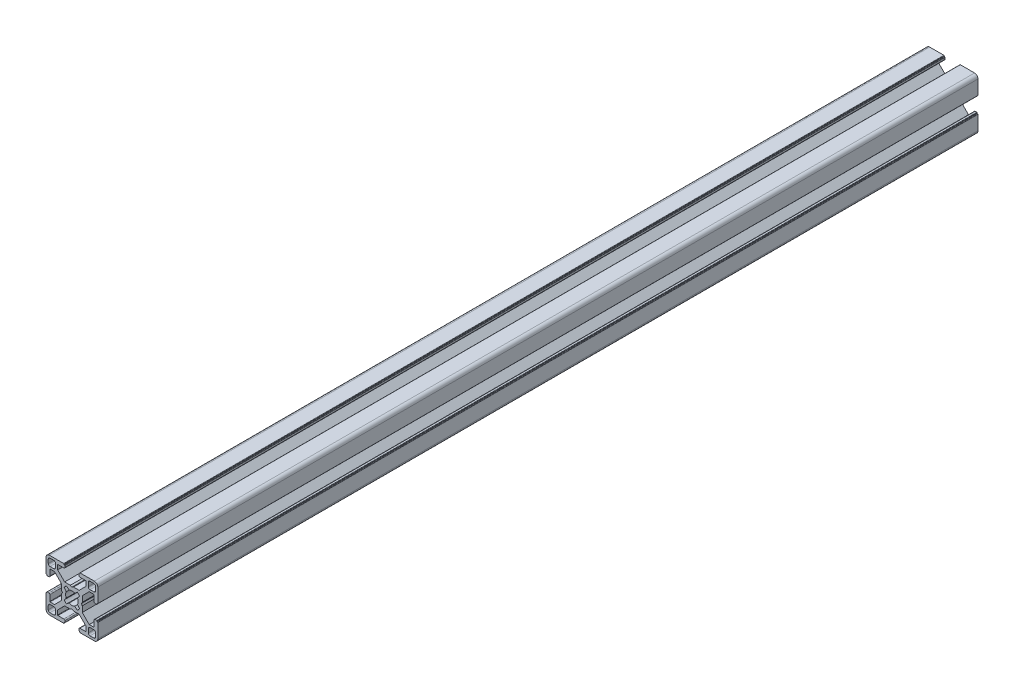
SolidWorks part; units mm, degrees
ref_plane "Płaszczyzna przednia" through (0, 0, 0) normal (0, 0, 1) x (1, 0, 0)
ref_plane "Płaszczyzna górna" through (0, 0, 0) normal (0, 1, 0) x (1, 0, 0)
ref_plane "Płaszczyzna prawa" through (0, 0, 0) normal (1, 0, 0) x (0, 0, -1)
sketch "Szkic1" plane through (0, 0, 0) normal (0, 0, 1) x (1, 0, 0)
  line L0 (109.26, 48.76) -> (107.06, 48.76)
  line L1 (106.06, 47.76) -> (106.06, 45.56)
  line L2 (107.06, 44.56) -> (109.26, 44.56)
  line L3 (110.26, 45.56) -> (110.26, 47.76)
  line L4 (94.9599, 38.3406) -> (93.4241, 39.5784)
  line L5 (92.0547, 38.2147) -> (93.2794, 36.6601)
  line L6 (93.2794, 33.4599) -> (92.0547, 31.9053)
  line L7 (93.4241, 30.5416) -> (94.9599, 31.7794)
  line L8 (98.1601, 31.7794) -> (99.6959, 30.5416)
  line L9 (101.0653, 31.9053) -> (99.8406, 33.4599)
  line L10 (99.8406, 36.6601) -> (101.0653, 38.2147)
  line L11 (99.6959, 39.5784) -> (98.1601, 38.3406)
  line L12 (83.86, 21.36) -> (86.06, 21.36)
  line L13 (87.06, 22.36) -> (87.06, 24.56)
  line L14 (86.06, 25.56) -> (83.86, 25.56)
  line L15 (82.86, 24.56) -> (82.86, 22.36)
  line L16 (110.26, 22.36) -> (110.26, 24.56)
  line L17 (109.26, 25.56) -> (107.06, 25.56)
  line L18 (106.06, 24.56) -> (106.06, 22.36)
  line L19 (86.06, 48.76) -> (83.86, 48.76)
  line L20 (82.86, 47.76) -> (82.86, 45.56)
  line L21 (83.86, 44.56) -> (86.06, 44.56)
  line L22 (87.06, 45.56) -> (87.06, 47.76)
  line L23 (107.06, 21.36) -> (109.26, 21.36)
  line L24 (96.56, 29.5751) -> (97.46, 29.06)
  line L25 (97.46, 29.06) -> (100.7645, 29.06)
  line L26 (100.7645, 29.06) -> (104.81, 25.01)
  line L27 (104.81, 25.01) -> (104.81, 22.46)
  line L28 (104.61, 22.26) -> (101.21, 22.26)
  line L29 (100.61, 21.66) -> (100.61, 20.76)
  line L30 (100.81, 20.56) -> (100.91, 20.56)
  line L31 (101.11, 20.36) -> (101.11, 20.26)
  line L32 (101.31, 20.06) -> (109.56, 20.06)
  line L33 (111.56, 22.06) -> (111.56, 30.31)
  line L34 (111.36, 30.51) -> (111.26, 30.51)
  line L35 (111.06, 30.71) -> (111.06, 30.81)
  line L36 (110.86, 31.01) -> (109.96, 31.01)
  line L37 (109.36, 30.41) -> (109.36, 27.01)
  line L38 (109.16, 26.81) -> (106.61, 26.81)
  line L39 (106.61, 26.81) -> (102.5645, 30.8555)
  line L40 (102.5645, 30.8555) -> (102.5645, 34.16)
  line L41 (102.5645, 34.16) -> (102.0449, 35.06)
  line L42 (102.0449, 35.06) -> (102.5645, 35.96)
  line L43 (102.5645, 35.96) -> (102.5645, 39.2645)
  line L44 (102.5645, 39.2645) -> (106.61, 43.31)
  line L45 (106.61, 43.31) -> (109.16, 43.31)
  line L46 (109.36, 43.11) -> (109.36, 39.71)
  line L47 (109.96, 39.11) -> (110.86, 39.11)
  line L48 (111.06, 39.31) -> (111.06, 39.41)
  line L49 (111.26, 39.61) -> (111.36, 39.61)
  line L50 (111.56, 39.81) -> (111.56, 48.06)
  line L51 (109.56, 50.06) -> (101.31, 50.06)
  line L52 (101.11, 49.86) -> (101.11, 49.76)
  line L53 (100.91, 49.56) -> (100.81, 49.56)
  line L54 (100.61, 49.36) -> (100.61, 48.46)
  line L55 (101.21, 47.86) -> (104.61, 47.86)
  line L56 (104.81, 47.66) -> (104.81, 45.11)
  line L57 (104.81, 45.11) -> (100.7645, 41.06)
  line L58 (100.7645, 41.06) -> (97.46, 41.06)
  line L59 (97.46, 41.06) -> (96.56, 40.5449)
  line L60 (96.56, 40.5449) -> (95.66, 41.06)
  line L61 (95.66, 41.06) -> (92.3555, 41.06)
  line L62 (92.3555, 41.06) -> (88.31, 45.11)
  line L63 (88.31, 45.11) -> (88.31, 47.66)
  line L64 (88.51, 47.86) -> (91.91, 47.86)
  line L65 (92.51, 48.46) -> (92.51, 49.36)
  line L66 (92.31, 49.56) -> (92.21, 49.56)
  line L67 (92.01, 49.76) -> (92.01, 49.86)
  line L68 (91.81, 50.06) -> (83.56, 50.06)
  line L69 (81.56, 48.06) -> (81.56, 39.81)
  line L70 (81.76, 39.61) -> (81.86, 39.61)
  line L71 (82.06, 39.41) -> (82.06, 39.31)
  line L72 (82.26, 39.11) -> (83.16, 39.11)
  line L73 (83.76, 39.71) -> (83.76, 43.11)
  line L74 (83.96, 43.31) -> (86.51, 43.31)
  line L75 (86.51, 43.31) -> (90.5555, 39.2645)
  line L76 (90.5555, 39.2645) -> (90.5555, 35.96)
  line L77 (90.5555, 35.96) -> (91.0751, 35.06)
  line L78 (91.0751, 35.06) -> (90.5555, 34.16)
  line L79 (90.5555, 34.16) -> (90.5555, 30.8555)
  line L80 (90.5555, 30.8555) -> (86.51, 26.81)
  line L81 (86.51, 26.81) -> (83.96, 26.81)
  line L82 (83.76, 27.01) -> (83.76, 30.41)
  line L83 (83.16, 31.01) -> (82.26, 31.01)
  line L84 (82.06, 30.81) -> (82.06, 30.71)
  line L85 (81.86, 30.51) -> (81.76, 30.51)
  line L86 (81.56, 30.31) -> (81.56, 22.06)
  line L87 (83.56, 20.06) -> (91.81, 20.06)
  line L88 (92.01, 20.26) -> (92.01, 20.36)
  line L89 (92.21, 20.56) -> (92.31, 20.56)
  line L90 (92.51, 20.76) -> (92.51, 21.66)
  line L91 (91.91, 22.26) -> (88.51, 22.26)
  line L92 (88.31, 22.46) -> (88.31, 25.01)
  line L93 (88.31, 25.01) -> (92.3555, 29.06)
  line L94 (92.3555, 29.06) -> (95.66, 29.06)
  line L95 (95.66, 29.06) -> (96.56, 29.5751)
  arc A0 (107.06, 48.76) -> (106.06, 47.76) centre (107.06, 47.76) ccw
  arc A1 (106.06, 45.56) -> (107.06, 44.56) centre (107.06, 45.56) ccw
  arc A2 (109.26, 44.56) -> (110.26, 45.56) centre (109.26, 45.56) ccw
  arc A3 (110.26, 47.76) -> (109.26, 48.76) centre (109.26, 47.76) ccw
  arc A4 (93.4241, 39.5784) -> (92.0547, 38.2147) centre (96.56, 35.06) ccw
  arc A5 (93.2794, 36.6601) -> (93.2794, 33.4599) centre (96.56, 35.06) ccw
  arc A6 (92.0547, 31.9053) -> (93.4241, 30.5416) centre (96.56, 35.06) ccw
  arc A7 (94.9599, 31.7794) -> (98.1601, 31.7794) centre (96.56, 35.06) ccw
  arc A8 (99.6959, 30.5416) -> (101.0653, 31.9053) centre (96.56, 35.06) ccw
  arc A9 (99.8406, 33.4599) -> (99.8406, 36.6601) centre (96.56, 35.06) ccw
  arc A10 (101.0653, 38.2147) -> (99.6959, 39.5784) centre (96.56, 35.06) ccw
  arc A11 (98.1601, 38.3406) -> (94.9599, 38.3406) centre (96.56, 35.06) ccw
  arc A12 (86.06, 21.36) -> (87.06, 22.36) centre (86.06, 22.36) ccw
  arc A13 (87.06, 24.56) -> (86.06, 25.56) centre (86.06, 24.56) ccw
  arc A14 (83.86, 25.56) -> (82.86, 24.56) centre (83.86, 24.56) ccw
  arc A15 (82.86, 22.36) -> (83.86, 21.36) centre (83.86, 22.36) ccw
  arc A16 (109.26, 21.36) -> (110.26, 22.36) centre (109.26, 22.36) ccw
  arc A17 (110.26, 24.56) -> (109.26, 25.56) centre (109.26, 24.56) ccw
  arc A18 (107.06, 25.56) -> (106.06, 24.56) centre (107.06, 24.56) ccw
  arc A19 (106.06, 22.36) -> (107.06, 21.36) centre (107.06, 22.36) ccw
  arc A20 (83.86, 48.76) -> (82.86, 47.76) centre (83.86, 47.76) ccw
  arc A21 (82.86, 45.56) -> (83.86, 44.56) centre (83.86, 45.56) ccw
  arc A22 (86.06, 44.56) -> (87.06, 45.56) centre (86.06, 45.56) ccw
  arc A23 (87.06, 47.76) -> (86.06, 48.76) centre (86.06, 47.76) ccw
  arc A24 (104.61, 22.26) -> (104.81, 22.46) centre (104.61, 22.46) ccw
  arc A25 (101.21, 22.26) -> (100.61, 21.66) centre (101.21, 21.66) ccw
  arc A26 (100.61, 20.76) -> (100.81, 20.56) centre (100.81, 20.76) ccw
  arc A27 (101.11, 20.36) -> (100.91, 20.56) centre (100.91, 20.36) ccw
  arc A28 (101.11, 20.26) -> (101.31, 20.06) centre (101.31, 20.26) ccw
  arc A29 (109.56, 20.06) -> (111.56, 22.06) centre (109.56, 22.06) ccw
  arc A30 (111.56, 30.31) -> (111.36, 30.51) centre (111.36, 30.31) ccw
  arc A31 (111.06, 30.71) -> (111.26, 30.51) centre (111.26, 30.71) ccw
  arc A32 (111.06, 30.81) -> (110.86, 31.01) centre (110.86, 30.81) ccw
  arc A33 (109.96, 31.01) -> (109.36, 30.41) centre (109.96, 30.41) ccw
  arc A34 (109.16, 26.81) -> (109.36, 27.01) centre (109.16, 27.01) ccw
  arc A35 (109.36, 43.11) -> (109.16, 43.31) centre (109.16, 43.11) ccw
  arc A36 (109.36, 39.71) -> (109.96, 39.11) centre (109.96, 39.71) ccw
  arc A37 (110.86, 39.11) -> (111.06, 39.31) centre (110.86, 39.31) ccw
  arc A38 (111.26, 39.61) -> (111.06, 39.41) centre (111.26, 39.41) ccw
  arc A39 (111.36, 39.61) -> (111.56, 39.81) centre (111.36, 39.81) ccw
  arc A40 (111.56, 48.06) -> (109.56, 50.06) centre (109.56, 48.06) ccw
  arc A41 (101.31, 50.06) -> (101.11, 49.86) centre (101.31, 49.86) ccw
  arc A42 (100.91, 49.56) -> (101.11, 49.76) centre (100.91, 49.76) ccw
  arc A43 (100.81, 49.56) -> (100.61, 49.36) centre (100.81, 49.36) ccw
  arc A44 (100.61, 48.46) -> (101.21, 47.86) centre (101.21, 48.46) ccw
  arc A45 (104.81, 47.66) -> (104.61, 47.86) centre (104.61, 47.66) ccw
  arc A46 (88.51, 47.86) -> (88.31, 47.66) centre (88.51, 47.66) ccw
  arc A47 (91.91, 47.86) -> (92.51, 48.46) centre (91.91, 48.46) ccw
  arc A48 (92.51, 49.36) -> (92.31, 49.56) centre (92.31, 49.36) ccw
  arc A49 (92.01, 49.76) -> (92.21, 49.56) centre (92.21, 49.76) ccw
  arc A50 (92.01, 49.86) -> (91.81, 50.06) centre (91.81, 49.86) ccw
  arc A51 (83.56, 50.06) -> (81.56, 48.06) centre (83.56, 48.06) ccw
  arc A52 (81.56, 39.81) -> (81.76, 39.61) centre (81.76, 39.81) ccw
  arc A53 (82.06, 39.41) -> (81.86, 39.61) centre (81.86, 39.41) ccw
  arc A54 (82.06, 39.31) -> (82.26, 39.11) centre (82.26, 39.31) ccw
  arc A55 (83.16, 39.11) -> (83.76, 39.71) centre (83.16, 39.71) ccw
  arc A56 (83.96, 43.31) -> (83.76, 43.11) centre (83.96, 43.11) ccw
  arc A57 (83.76, 27.01) -> (83.96, 26.81) centre (83.96, 27.01) ccw
  arc A58 (83.76, 30.41) -> (83.16, 31.01) centre (83.16, 30.41) ccw
  arc A59 (82.26, 31.01) -> (82.06, 30.81) centre (82.26, 30.81) ccw
  arc A60 (81.86, 30.51) -> (82.06, 30.71) centre (81.86, 30.71) ccw
  arc A61 (81.76, 30.51) -> (81.56, 30.31) centre (81.76, 30.31) ccw
  arc A62 (81.56, 22.06) -> (83.56, 20.06) centre (83.56, 22.06) ccw
  arc A63 (91.81, 20.06) -> (92.01, 20.26) centre (91.81, 20.26) ccw
  arc A64 (92.21, 20.56) -> (92.01, 20.36) centre (92.21, 20.36) ccw
  arc A65 (92.31, 20.56) -> (92.51, 20.76) centre (92.31, 20.76) ccw
  arc A66 (92.51, 21.66) -> (91.91, 22.26) centre (91.91, 21.66) ccw
  arc A67 (88.31, 22.46) -> (88.51, 22.26) centre (88.51, 22.46) ccw
  dimension "D1" = 3.65
  dimension "D2" = 30
  dimension "D3" = 30
  dimension "D4" = 8.1
extrude "Dodanie-wyciągnięcie1" add sketch "Szkic1" along normal blind 510
